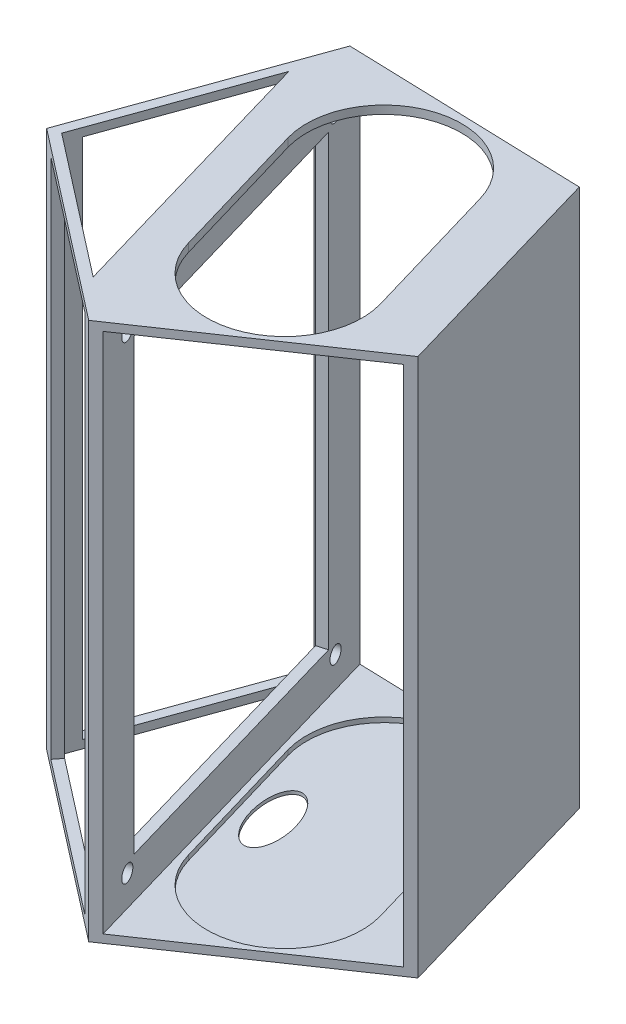
SolidWorks part; units mm, degrees
ref_plane "Front Plane" through (0, 0, 0) normal (0, 0, 1) x (1, 0, 0)
ref_plane "Top Plane" through (0, 0, 0) normal (0, 1, 0) x (1, 0, 0)
ref_plane "Right Plane" through (0, 0, 0) normal (1, 0, 0) x (0, 0, -1)
sketch "Sketch1" plane through (0, 0, 0) normal (0, 1, 0) x (1, 0, 0)
  line L1 (23.2611, -8.3705) -> (15.1489, 19.536)
  line L2 (15.1489, 19.536) -> (-13.8986, 20.4445)
  line L3 (-13.8986, 20.4445) -> (-23.7387, -6.9006)
  line L4 (-23.7387, -6.9006) -> (-0.7728, -24.7093)
  line L5 (-0.7728, -24.7093) -> (23.2611, -8.3705)
  circle A0 centre (0, 0) radius 20 construction
  point P1 (0, 0)
extrude "Boss-Extrude1" add sketch "Sketch1" along normal blind 1
sketch "Sketch2" plane through (0, 1, 0) normal (0, 1, 0) x (1, 0, 0)
  line L0 (-0.7728, -24.7093) -> (-13.8986, 20.4445) construction
  line L1 (-2.9239, -23.0412) -> (-14.8202, 17.8832)
  line L2 (-23.7387, -6.9006) -> (-0.7728, -24.7093) construction
  line L3 (-13.8986, 20.4445) -> (-23.7387, -6.9006) construction
  line L4 (0.2707, -23.9999) -> (-12.6374, 20.405)
  line L5 (-0.7728, -24.7093) -> (23.2611, -8.3705) construction
  line L6 (15.1489, 19.536) -> (-13.8986, 20.4445) construction
  line L7 (-14.8202, 17.8832) -> (-13.8986, 20.4445)
  line L13 (-0.7728, -24.7093) -> (23.2611, -8.3705)
  line L14 (23.2611, -8.3705) -> (15.1489, 19.536)
  line L15 (15.1489, 19.536) -> (-13.8986, 20.4445)
  line L16 (-13.8986, 20.4445) -> (-23.7387, -6.9006)
  line L17 (-23.7387, -6.9006) -> (-0.7728, -24.7093)
  line L18 (-0.7728, -24.7093) -> (0.2707, -23.9999)
  line L20 (-12.6374, 20.405) -> (-13.8986, 20.4445)
  line L21 (-13.8986, 20.4445) -> (-14.8202, 17.8832)
  line L22 (-2.9239, -23.0412) -> (-0.7728, -24.7093)
  line M10 (-0.7728, -24.7093) -> (23.2611, -8.3705)
  line M12 (15.1489, 19.536) -> (-13.8986, 20.4445)
  line M13 (-13.8986, 20.4445) -> (-23.7387, -6.9006)
  line M14 (-23.7387, -6.9006) -> (-0.7728, -24.7093)
  dimension "D1" = 1.2
  dimension "D2" = 1.6
  dimension "D3" = 0
extrude "Boss-Extrude2" add sketch "Sketch2" along normal blind 65 contours L0 L1 M14 M13 | L0 L4 M10 M12 region at (-8.0913, 1, 2.3521) region at (-6.7611, 1, 1.9654)
sketch "Sketch3" plane through (0, 1, 0) normal (0, 1, 0) x (1, 0, 0)
  line L0 (10.2933, 12.2338) -> (15.3581, -5.0389)
  line L3 (-7.9391, 6.8877) -> (-2.8743, -10.3851)
  line L4 (-23.7201, -6.9646) -> (0.0025, -0.0086) construction
  line L5 (6.2419, -7.712) -> (1.1771, 9.5607) construction
  arc A0 (15.3581, -5.0389) -> (-2.8743, -10.3851) centre (6.2419, -7.712) cw
  arc A1 (10.2933, 12.2338) -> (-7.9391, 6.8877) centre (1.1771, 9.5607) ccw
  point P6 (-1.496, 18.6769)
  point P7 (8.915, -16.8282)
  dimension "D1" = 37
  dimension "D2" = 19
sketch "Sketch4" plane through (-8.8721, 0, 2.579) normal (-0.9603, 0, 0.2791) x (0.2791, 0, 0.9603)
  line L0 (-21.3092, 66) -> (21.3092, 1) construction
  line L1 (21.3092, 1) -> (-21.3092, 1) construction
  line L2 (21.3092, 66) -> (-21.3092, 1) construction
  line L3 (0, 63.5) -> (0, 3.5) construction
  line L4 (-20, 63.5) -> (20, 63.5)
  line L5 (-20, 63.5) -> (-20, 3.5)
  line L6 (-20, 3.5) -> (20, 3.5)
  line L7 (20, 63.5) -> (20, 3.5)
  line L8 (-20, 63.5) -> (20, 3.5) construction
  line L9 (-20, 3.5) -> (20, 63.5) construction
  line L10 (-20, 33.5) -> (20, 33.5) construction
  point P12 (0, 33.5)
  dimension "D1" = 40
  dimension "D2" = 60
extrude "Cut-Extrude1" cut sketch "Sketch4" against normal blind 1.5
sketch "Sketch5" plane through (-7.4317, 0, 2.1603) normal (-0.9603, 0, 0.2791) x (0.2791, 0, 0.9603)
  line L8 (17.5, 6) -> (17.5, 61)
  line L9 (17.5, 61) -> (-17.5, 61)
  line L10 (-17.5, 61) -> (-17.5, 6)
  line L11 (-17.5, 6) -> (17.5, 6)
  line L12 (17.5, 6) -> (17.5, 61)
  line L13 (17.5, 61) -> (-17.5, 61)
  line L14 (-17.5, 61) -> (-17.5, 6)
  line L15 (-17.5, 6) -> (17.5, 6)
  dimension "D1" = 2.5
extrude "Cut-Extrude2" cut sketch "Sketch5" against normal up to surface (1.3 mm away) up to face at (-6.1834, 33.5, 1.7974)
sketch "Sketch7" plane through (0, 66, 0) normal (0, 1, 0) x (1, 0, 0)
  line L5 (-0.7728, -24.7093) -> (23.2611, -8.3705)
  line L6 (-23.7387, -6.9006) -> (-0.7728, -24.7093)
  line L7 (-13.8986, 20.4445) -> (-23.7387, -6.9006)
  line L8 (15.1489, 19.536) -> (-13.8986, 20.4445)
  line L9 (23.2611, -8.3705) -> (15.1489, 19.536)
  line L10 (-0.7728, -24.7093) -> (23.2611, -8.3705)
  line L11 (-23.7387, -6.9006) -> (-0.7728, -24.7093)
  line L12 (-13.8986, 20.4445) -> (-23.7387, -6.9006)
  line L13 (15.1489, 19.536) -> (-13.8986, 20.4445)
  line L14 (23.2611, -8.3705) -> (15.1489, 19.536)
  dimension "D1" = 0
extrude "Boss-Extrude3" add sketch "Sketch7" against normal blind 1
sketch "Sketch6" plane through (0, 1, 0) normal (0, 1, 0) x (1, 0, 0)
  line L6 (-22.3144, -6.4866) -> (-5.1071, -19.8298)
  line L7 (-5.1071, -19.8298) -> (-14.9416, 14.0018)
  line L8 (-14.9416, 14.0018) -> (-22.3144, -6.4866)
  line L9 (-22.3144, -6.4866) -> (-5.1071, -19.8298)
  line L10 (-5.1071, -19.8298) -> (-14.9416, 14.0018)
  line L11 (-14.9416, 14.0018) -> (-22.3144, -6.4866)
  dimension "D1" = 1.2
extrude "Cut-Extrude3" cut sketch "Sketch6" along normal up to surface and the other way up to surface up to face at (0, 66, 0) other way up to face at (0, 0, 0)
extrude "Cut-Extrude4" cut sketch "Sketch3" against normal blind 0.6 and the other way up to surface (65 mm away) other way up to face at (0, 66, 0)
sketch "Sketch8" plane through (-7.4317, 0, 2.1603) normal (-0.9603, 0, 0.2791) x (0.2791, 0, 0.9603)
  line L0 (0, 3.5) -> (0, 63.5) construction
  line L1 (-20, 3.5) -> (20, 3.5) construction
  line L2 (20, 63.5) -> (-20, 63.5) construction
  line L3 (-20, 33.5) -> (20, 33.5) construction
  line L4 (-20, 63.5) -> (-20, 3.5) construction
  line L5 (20, 3.5) -> (20, 63.5) construction
  circle A0 centre (-18.75, 4.75) radius 1
  circle A1 centre (18.75, 4.75) radius 1
  circle A2 centre (-18.75, 62.25) radius 1
  circle A3 centre (18.75, 62.25) radius 1
  dimension "D1" = 2
  dimension "D2" = 1.25
  dimension "D3" = 1.25
extrude "Cut-Extrude5" cut sketch "Sketch8" against normal up to surface (1.3 mm away) up to face at (-6.1834, 33.5, 1.7974)
sketch "Sketch9" plane through (0, 1, 0) normal (0, 1, 0) x (1, 0, 0)
  line L0 (-23.7387, -6.9006) -> (-22.3144, -6.4866) construction
  line L1 (-21.6372, -4.6047) -> (-22.7663, -4.1984)
  line L6 (-22.3144, -6.4866) -> (-14.9416, 14.0018) construction
  line L7 (-14.8202, 17.8832) -> (-23.7387, -6.9006) construction
  line L8 (-20.7339, -7.7122) -> (-21.4692, -8.6605)
  line L9 (-5.1071, -19.8298) -> (-22.3144, -6.4866) construction
  line L10 (-23.7387, -6.9006) -> (-2.9239, -23.0412) construction
  line L11 (-21.6372, -4.6047) -> (-22.3144, -6.4866)
  line L12 (-22.3144, -6.4866) -> (-20.7339, -7.7122)
  line L13 (-21.4692, -8.6605) -> (-23.7387, -6.9006)
  line L14 (-23.7387, -6.9006) -> (-22.7663, -4.1984)
  line L15 (23.2611, -8.3705) -> (15.1489, 19.536)
  line L16 (15.1489, 19.536) -> (13.8878, 19.5754)
  line L17 (15.1489, 19.536) -> (-12.6374, 20.405) construction
  line L18 (13.8878, 19.5754) -> (22.2177, -9.0799)
  line L19 (0.2707, -23.9999) -> (23.2611, -8.3705) construction
  line L20 (22.2177, -9.0799) -> (23.2611, -8.3705)
  dimension "D1" = 2
  dimension "D2" = 2
  dimension "D3" = 1.2
extrude "Boss-Extrude4" add sketch "Sketch9" along normal up to surface (64 mm away) up to face at (6.5108, 65, -1.8926)
sketch "Sketch10" plane through (0, 0.4, 0) normal (0, 1, 0) x (1, 0, 0)
  line L0 (-5.4067, -1.7487) -> (12.8257, 3.5974) construction
  line L1 (-7.9391, 6.8877) -> (-2.8743, -10.3851) construction
  line L2 (15.3581, -5.0389) -> (10.2933, 12.2338) construction
  ellipse E0 centre (-2.085, -0.7747) end of major axis (-3.4126, 3.7527) minor radius 2.25
  dimension "D1" = 4.5
extrude "Cut-Extrude6" cut sketch "Sketch10" against normal up to surface (0.4 mm away) up to face at (0, 0, 0)
